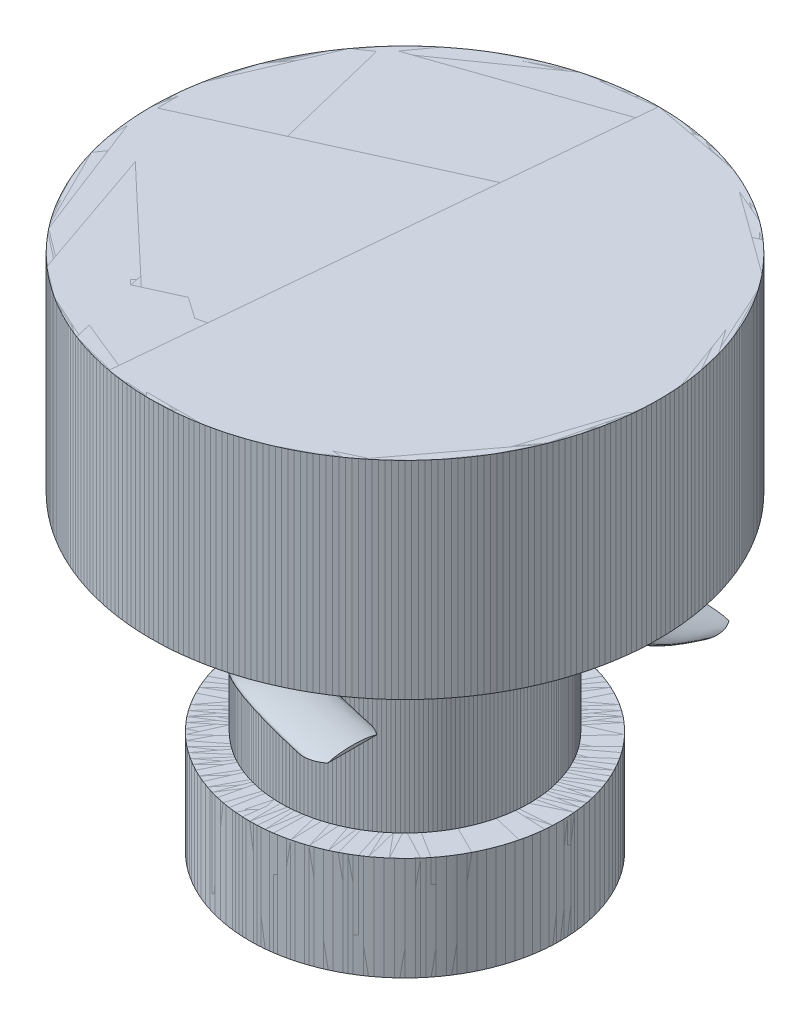
SolidWorks part; units mm, degrees
ref_plane "Front Plane" through (0, 0, 0) normal (0, 0, 1) x (1, 0, 0)
ref_plane "Top Plane" through (0, 0, 0) normal (0, 1, 0) x (1, 0, 0)
ref_plane "Right Plane" through (0, 0, 0) normal (1, 0, 0) x (0, 0, -1)
sketch "Sketch1" plane through (0, 0, 0) normal (0, 0, 1) x (1, 0, 0)
  line L0 (0, 0) -> (6.223, 0)
  line L1 (6.223, 0) -> (6.223, -5.08)
  line L2 (6.223, -5.08) -> (3.048, -5.08)
  line L3 (3.048, -5.08) -> (3.048, -10.16)
  line L4 (3.048, -10.16) -> (3.81, -10.16)
  line L5 (3.81, -10.16) -> (3.81, -12.7)
  line L6 (3.81, -12.7) -> (0, -12.7)
  line L7 (0, -12.7) -> (0, 0)
  dimension "D1" = 12.7
  dimension "D2" = 2.54
  dimension "D3" = 5.08
  dimension "D4" = 6.223
  dimension "D5" = 3.048
  dimension "D6" = 3.81
revolve "button body" add sketch "Sketch1" angle 360 about L7
ref_plane "spring path" through (4.318, 0, 0) normal (1, 0, 0) x (0, 0, -1)
sketch "Sketch2" plane through (4.318, 0, 0) normal (1, 0, 0) x (0, 0, -1)
  spline S0 degree 3 poles (2.9542, -4.563) (1.8538, -5.2739) (-1.4839, -5.7786) (3.0242, -6.9827) knots 0 0 0 0 1 1 1 1
ref_plane "spring cross section" through (0, 0, -3.0242) normal (0, 0, 1) x (1, 0, 0)
sketch "Sketch4" plane through (0, 0, -3.0242) normal (0, 0, 1) x (1, 0, 0)
  ellipse E0 centre (4.318, -6.9827) end of major axis (3.556, -6.9827) minor radius 0.2032
  dimension "D1" = 0
sweep "spring" add profiles "Sketch4" path "Sketch2"
ref_axis "center axis" through (0, 0, 0) along (0, -1, 0)
pattern_circular "moar springs" count 4 over 360 about axis through (0, 0, 0) along (0, -1, 0) of bodies 102
ref_plane "spring cutoff" through (0, -6.858, 0) normal (0, 1, 0) x (1, 0, 0)
sketch "Sketch5" plane through (0, -6.858, 0) normal (0, 1, 0) x (1, 0, 0)
  line L1 (-5.4573, -1.4157) -> (-3.0941, -1.4157)
  line L2 (-5.4573, -1.4157) -> (-5.4573, -3.506)
  line L3 (-5.4573, -3.506) -> (-3.0941, -3.506)
  line L4 (-3.0941, -1.4157) -> (-3.0941, -3.506)
  line L5 (1.4555, -3.3381) -> (3.3946, -3.3381)
  line L6 (1.4555, -3.3381) -> (1.4555, -5.4537)
  line L7 (1.4555, -5.4537) -> (3.3946, -5.4537)
  line L8 (3.3946, -3.3381) -> (3.3946, -5.4537)
  line L9 (3.3946, 3.1587) -> (5.2632, 3.1587)
  line L10 (3.3946, 3.1587) -> (3.3946, 1.2698)
  line L11 (3.3946, 1.2698) -> (5.2632, 1.2698)
  line L12 (5.2632, 3.1587) -> (5.2632, 1.2698)
  line L13 (-3.4934, 5.5558) -> (-1.1945, 5.5558)
  line L14 (-3.4934, 5.5558) -> (-3.4934, 3.1587)
  line L15 (-3.4934, 3.1587) -> (-1.1945, 3.1587)
  line L16 (-1.1945, 5.5558) -> (-1.1945, 3.1587)
extrude "flatten springs" cut sketch "Sketch5" along direction (0, 1, 0) on the side against the normal up to surface (3.302 mm away) up to face at (-3.048, -10.16, 0)
